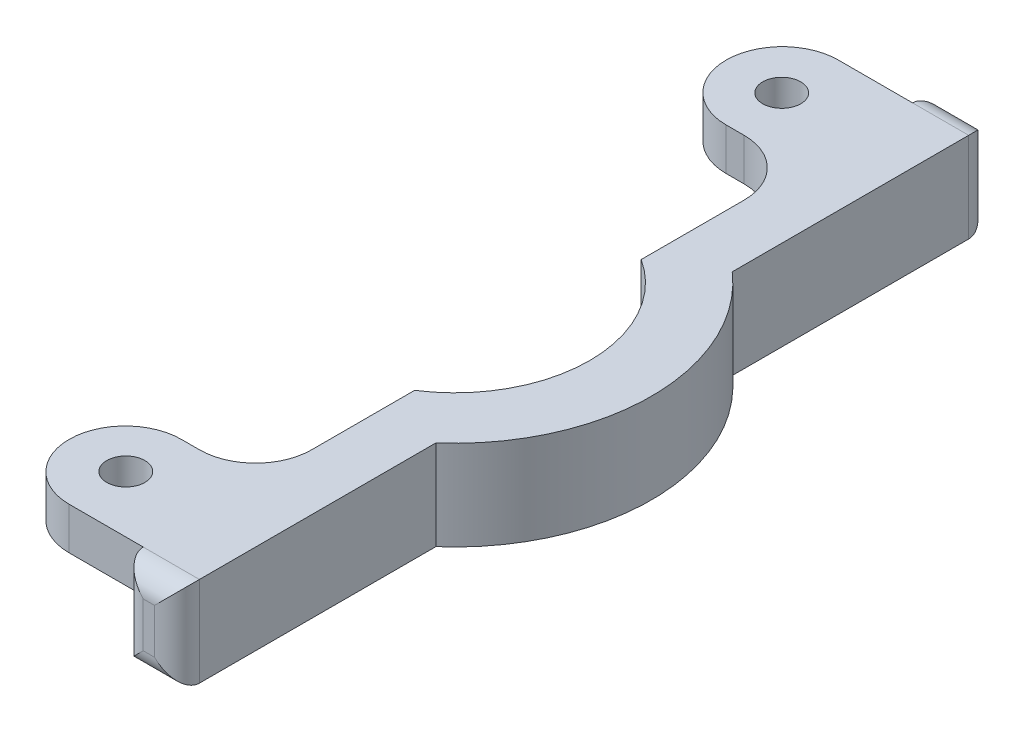
SolidWorks part; units mm, degrees
material "reg_restraint_mat"
ref_plane "Front Plane" through (0, 0, 0) normal (0, 0, 1) x (1, 0, 0)
ref_plane "Top Plane" through (0, 0, 0) normal (0, 1, 0) x (1, 0, 0)
ref_plane "Right Plane" through (0, 0, 0) normal (1, 0, 0) x (0, 0, -1)
sketch "Sketch1" plane through (0, 0, 0) normal (0, 1, 0) x (1, 0, 0)
  circle A0 centre (0, 0) radius 15.24
  circle A1 centre (0, 0) radius 22.225
  dimension "D1" = 30.48
  dimension "D2" = 44.45
extrude "Boss-Extrude1" add sketch "Sketch1" along normal blind 5.08
sketch "Sketch2" plane through (0, 5.08, 0) normal (0, 1, 0) x (1, 0, 0)
  line L0 (75.9534, -6.4389) -> (38.5188, -6.4389)
  line L1 (82.3034, -0.0889) -> (82.3034, 0.0889)
  line L3 (75.9534, 6.4389) -> (38.5188, 6.4389)
  line L4 (82.3034, -6.4389) -> (38.5188, 6.4389) construction
  line L5 (38.5188, -6.4389) -> (82.3034, 6.4389) construction
  line L6 (38.5188, 6.4389) -> (17.5908, 6.4389)
  line L7 (60.4111, 0) -> (0, 0) construction
  line L11 (38.5188, -6.4389) -> (17.5908, -6.4389)
  line L12 (17.5908, 6.4389) -> (17.5908, -6.4389)
  arc A0 (82.3034, -0.0889) -> (75.9534, -6.4389) centre (75.9534, -0.0889) cw
  arc A1 (82.3034, 0.0889) -> (75.9534, 6.4389) centre (75.9534, 0.0889) ccw
  point P1 (60.4111, 0)
  dimension "D4" = 6.35
  dimension "D3" = 12.8778
extrude "Boss-Extrude2" [suppressed] add sketch "Sketch2" against normal blind 3.175
hole_wizard "F (0.257) Diameter Hole1" [suppressed] positions "Sketch3" profile "Sketch4" hole size "F" standard "ANSI Inch"
sketch "Sketch3" plane through (0, 3.175, 0) normal (0, 1, 0) x (1, 0, 0)
  line L0 (0, 0) -> (69.85, 0) construction
  point P0 (69.85, 0)
  dimension "D1" = 69.85
sketch "Sketch4" plane through (69.85, 3.175, 0) normal (1, 0, 0) x (0, 0, 1)
  line L0 (0, 0) -> (0, 3.175)
  line L1 (0, 3.175) -> (3.2639, 3.175)
  line L2 (3.2639, 3.175) -> (3.2639, 0)
  line L5 (3.2639, 0) -> (0, 0)
  line L11 (0, -6.35) -> (0, 107.95) construction
  dimension "Thru Hole Dia." = 6.5278
  dimension "Thru Hole Depth" = 3.175
sketch "Sketch6" plane through (0, 5.08, 0) normal (0, 1, 0) x (1, 0, 0)
  line L0 (8.255, 0) -> (15.24, 0) construction
  line L1 (8.255, -42.2389) -> (8.255, 39.9322)
  line L2 (8.255, -42.2389) -> (-56.6624, -42.2389)
  line L3 (8.255, 39.9322) -> (-56.6624, 39.9322)
  line L4 (-56.6624, -42.2389) -> (-56.6624, 39.9322)
  circle A1 centre (0, 0) radius 15.24 construction
  dimension "D1" = 6.985
extrude "Cut-Extrude2" cut sketch "Sketch6" against normal through all
fillet "Fillet2" [suppressed] radius 2.54
sketch "Sketch9" plane through (0, 5.08, 0) normal (0, 1, 0) x (1, 0, 0)
  line L0 (8.255, 20.6351) -> (8.255, 46.0351)
  line L1 (8.255, 46.0351) -> (14.605, 46.0351)
  line L2 (14.605, 46.0351) -> (14.605, 16.7525)
  line L3 (8.255, 20.6351) -> (14.605, 16.7525)
  arc A0 (8.255, -20.6351) -> (8.255, 20.6351) centre (0, 0) ccw construction
  dimension "D1" = 6.35
  dimension "D2" = 25.4
extrude "Boss-Extrude3" add sketch "Sketch9" against normal blind 5.08
mirror "Mirror1" about plane through (0, 0, 0) normal (0, 0, 1) of "Boss-Extrude3"
fillet "Fillet4" [suppressed] radius 1.27
sketch "Sketch11" plane through (0, 5.08, 0) normal (0, 1, 0) x (1, 0, 0)
  line L0 (59.4458, 0) -> (22.9162, 0) construction
  line L1 (59.4458, -3.6155) -> (22.9162, -3.6155)
  line L2 (59.4458, 3.6155) -> (22.9162, 3.6155)
  line L3 (15.24, 0) -> (64.7315, 0) construction
  arc A0 (59.4458, -3.6155) -> (59.4458, 3.6155) centre (59.4458, 0) ccw
  arc A1 (22.9162, 3.6155) -> (22.9162, -3.6155) centre (22.9162, 0) ccw
  arc A2 (8.255, -12.8106) -> (8.255, 12.8106) centre (0, 0) ccw construction
  point P2 (41.181, 0)
extrude "Cut-Extrude3" [suppressed] cut sketch "Sketch11" against normal through all
sketch "Sketch12" plane through (14.605, 0, 0) normal (1, 0, 0) x (0, 0, -1)
  line L0 (0, 2.794) -> (0, -2.794) construction
  line L2 (16.7525, 0) -> (46.0351, 0) construction
  circle A0 centre (38.1, 0) radius 2.1527
  circle A1 centre (-38.1, 0) radius 2.1527
  dimension "D1" = 4.3053
  dimension "D2" = 38.1
extrude "Cut-Extrude4" [suppressed] cut sketch "Sketch12" against normal through all
sketch "Sketch13" [suppressed] plane through (0, 3.175, 0) normal (0, 1, 0) x (1, 0, 0)
  circle A0 centre (69.85, 0) radius 3.2639
  circle A1 centre (69.85, 0) radius 5.8039
  dimension "D1" = 2.54
extrude "Boss-Extrude4" [suppressed] add sketch "Sketch13" along normal blind 9.525
mirror "Mirror2" about plane through (0, 0, 0) normal (0, 1, 0) of "Boss-Extrude1", "Boss-Extrude2", "F (0.257) Diameter Hole1", "Cut-Extrude2", "Boss-Extrude3", "Mirror1", "Cut-Extrude4"
fillet "Fillet5" radius 2.54 8 edges at (14.605, 0, 46.0351) (11.43, -5.08, 46.0351) (8.255, 0, 46.0351) (11.43, 5.08, 46.0351) (8.255, 0, -46.0351) (11.43, -5.08, -46.0351) (14.605, 0, -46.0351) (11.43, 5.08, -46.0351)
sketch "Sketch15" plane through (8.255, 0, 0) normal (-1, 0, 0) x (0, 0, 1)
  line L1 (-43.4951, 5.08) -> (-30.7951, 5.08)
  line L2 (-43.4951, 5.08) -> (-43.4951, 0.3175)
  line L3 (-43.4951, 0.3175) -> (-30.7951, 0.3175)
  line L4 (-30.7951, 5.08) -> (-30.7951, 0.3175)
  dimension "D1" = 4.7625
  dimension "D2" = 12.7
extrude "Boss-Extrude5" add sketch "Sketch15" along normal blind 14.732
sketch "Sketch17" plane through (0, 5.08, 0) normal (0, 1, 0) x (1, 0, 0)
  line L0 (-6.477, 37.1451) -> (14.605, 37.1451) construction
  line L1 (-6.477, 30.7951) -> (-6.477, 43.4951) construction
  line L2 (14.605, 16.7525) -> (14.605, 43.4951) construction
  line L3 (8.255, 12.8106) -> (8.255, 30.7951) construction
  circle A0 centre (-0.127, 37.084) radius 2.1527
  dimension "D1" = 4.3053
  dimension "D2" = 8.382
  dimension "D3" = 37.084
extrude "Cut-Extrude5" cut sketch "Sketch17" against normal blind 12.7
fillet "Fillet6" radius 6.35 3 edges at (8.255, 2.6987, -30.7951) (-6.477, 2.6987, -30.7951) (-6.477, 2.6987, -43.4951)
mirror "Mirror3" about plane through (0, 0, 0) normal (0, 0, 1) of "Fillet6", "Boss-Extrude5", "Cut-Extrude5"
